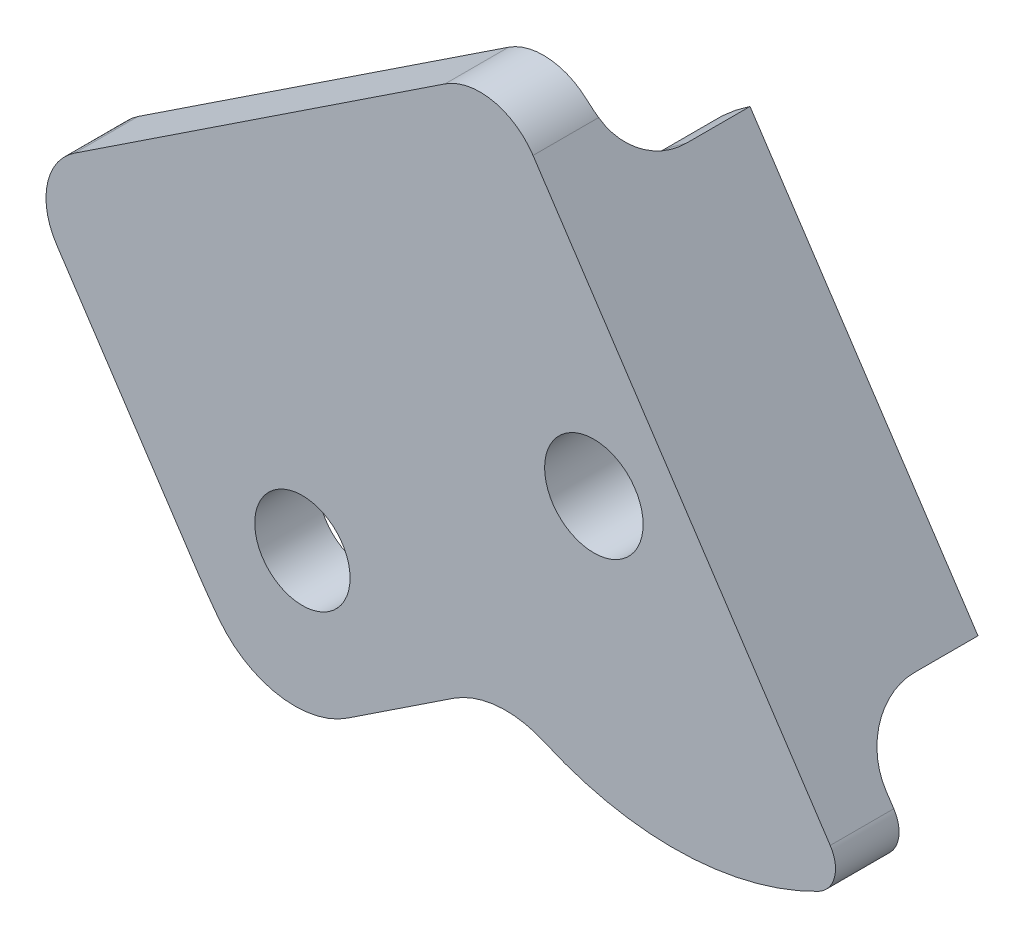
SolidWorks part; units mm, degrees
material "3003-H16"
ref_plane "前视基准面" through (0, 0, 0) normal (0, 0, 1) x (1, 0, 0)
ref_plane "上视基准面" through (0, 0, 0) normal (0, 1, 0) x (1, 0, 0)
ref_plane "右视基准面" through (0, 0, 0) normal (1, 0, 0) x (0, 0, -1)
other "Configuration Table"
sketch "草图2" plane through (0, 0, 0) normal (0, 0, 1) x (1, 0, 0)
  line L0 (14.565, -11.6696) -> (7.3898, -0.8291)
  line L1 (3.5263, 5.0081) -> (-3.6489, 15.8486)
  line L2 (-11.4038, 7.7177) -> (-14.736, 5.5122)
  line L3 (-15.0578, 0.5024) -> (-4.019, -16.1753)
  line L4 (0.7182, -17.8366) -> (4.0504, -15.6311)
  line L5 (15.9141, -13.7079) -> (15.1169, -12.5035)
  line L6 (6.8379, 0.0048) -> (4.0782, 4.1742)
  line L7 (-4.2009, 16.6825) -> (-4.998, 17.8869)
  line L8 (-4.2009, 16.6825) -> (-3.6489, 15.8486)
  line L9 (3.5263, 5.0081) -> (4.0782, 4.1742)
  line L10 (6.8379, 0.0048) -> (7.3898, -0.8291)
  line L11 (14.565, -11.6696) -> (15.1169, -12.5035)
  arc A0 (-11.4038, 7.7177) -> (-10.06, 10.2676) centre (-13.0597, 10.2194) ccw
  arc A1 (-14.736, 5.5122) -> (-15.6868, 1.5254) centre (-13.0802, 3.0106) ccw
  arc A2 (-15.6868, 1.5254) -> (-15.0578, 0.5024) centre (-0.0613, 10.4284) ccw
  arc A3 (-4.019, -16.1753) -> (-3.3232, -17.154) centre (10.9774, -6.2494) ccw
  arc A4 (-3.3232, -17.154) -> (0.7182, -17.8366) centre (-0.9376, -15.3349) ccw
  arc A5 (6.9226, -15.3904) -> (4.0504, -15.6311) centre (5.7062, -18.1327) ccw
  arc A6 (6.9226, -15.3904) -> (15.5361, -15.1498) centre (10.9774, -6.2494) ccw
  arc A7 (15.5361, -15.1498) -> (15.9141, -13.7079) centre (15.0802, -14.2598) ccw
  arc A10 (-4.998, 17.8869) -> (-6.4731, 18.1023) centre (-5.8319, 17.3349) ccw
  arc A11 (-6.4731, 18.1023) -> (-10.06, 10.2676) centre (-0.0613, 10.4284) ccw
  arc A12 (-1.2705, 9.628) -> (-3.8555, 7.917) centre (-2.563, 8.7725) ccw
  arc A13 (-3.8555, 7.917) -> (-1.2705, 9.628) centre (-2.563, 8.7725) ccw
  arc A14 (7.1832, -8.7607) -> (9.7683, -7.0497) centre (8.4757, -7.9052) ccw
  arc A15 (9.7683, -7.0497) -> (7.1832, -8.7607) centre (8.4757, -7.9052) ccw
  arc A16 (-1.9478, -14.8044) -> (0.5538, -13.1486) centre (-0.697, -13.9765) ccw
  arc A17 (0.5538, -13.1486) -> (-1.9478, -14.8044) centre (-0.697, -13.9765) ccw
  arc A18 (-10.4849, 3.5291) -> (-12.9866, 1.8733) centre (-11.7357, 2.7012) ccw
  arc A19 (-12.9866, 1.8733) -> (-10.4849, 3.5291) centre (-11.7357, 2.7012) ccw
extrude "凸台-拉伸1" add sketch "草图2" along normal blind 2
sketch "草图3" plane through (0, 0, 0) normal (0, 0, -1) x (-1, 0, 0)
  line L0 (3.6489, 15.8486) -> (-14.565, -11.6696)
  line L1 (-15.9141, -13.7079) -> (4.998, 17.8869) construction
  arc A0 (-3.5263, 5.0081) -> (3.6489, 15.8486) centre (0.0613, 10.4284) ccw
  arc A1 (-14.565, -11.6696) -> (-7.3898, -0.8291) centre (-10.9774, -6.2494) ccw
  circle A2 centre (2.563, 8.7725) radius 1.55
  circle A3 centre (-8.4757, -7.9052) radius 1.55
  line M2 (4.998, 17.8869) -> (-15.9141, -13.7079)
  circle M15 centre (2.563, 8.7725) radius 1.55
  circle M16 centre (-8.4757, -7.9052) radius 1.55
  dimension "D1" = 13
  dimension "D2" = 13
extrude "凸台-拉伸2" add sketch "草图3" along normal blind 4 contours A0 M2 M15 | A1 M2 M16 region at (-5.3514, 6.927, 0) region at (5.6874, -9.7508, 0)
fillet "圆角1" radius 2 2 edges at (5.5571, -9.837, 0) (-5.4816, 6.8408, 0)
sketch "草图4" plane through (0, 0, 2) normal (0, 0, 1) x (1, 0, 0)
  line L0 (5.458, 2.0895) -> (-9.5384, -7.8364)
  line L1 (15.9141, -13.7079) -> (-4.998, 17.8869) construction
  line L2 (-15.0578, 0.5024) -> (-4.019, -16.1753) construction
  line L3 (5.458, 2.0895) -> (-0.3936, 27.8791)
  line L4 (-0.3936, 27.8791) -> (-26.5453, 2.7332)
  line L5 (-26.5453, 2.7332) -> (-9.5384, -7.8364)
extrude "切除-拉伸1" cut sketch "草图4" against normal blind 10
fillet "圆角2" radius 2 2 edges at (5.458, 2.0895, 1) (-9.5384, -7.8364, 1)
